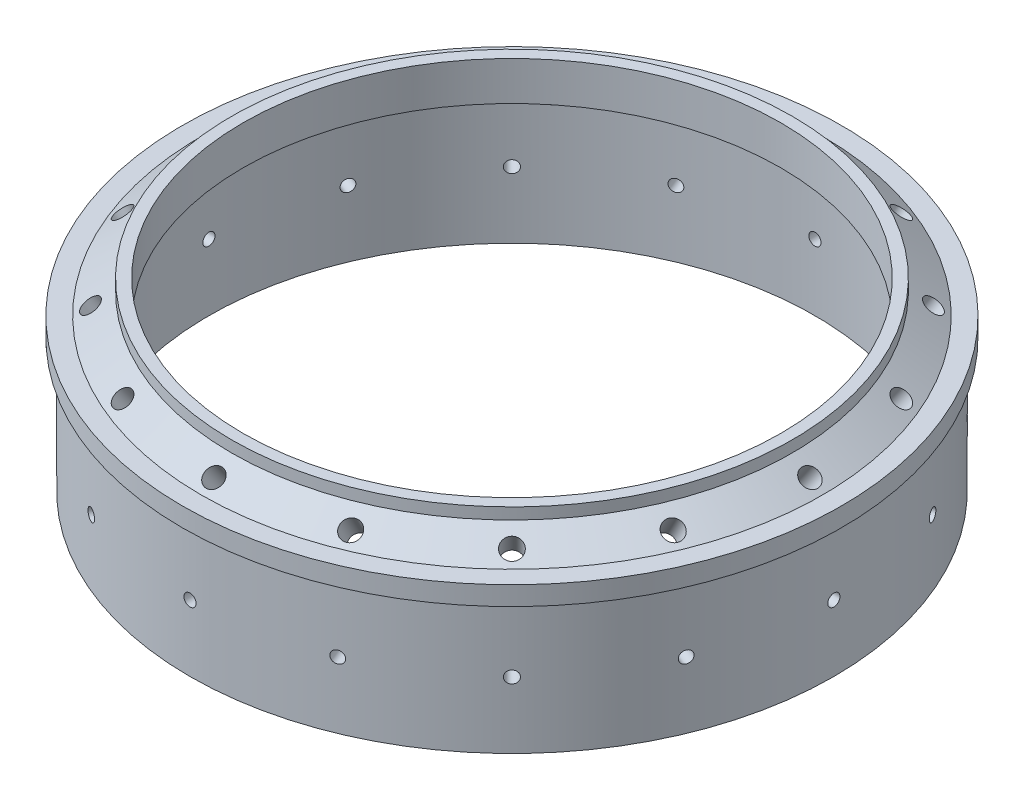
SolidWorks part; units mm, degrees
ref_plane "Front Plane" through (0, 0, 0) normal (0, 0, 1) x (1, 0, 0)
ref_plane "Top Plane" through (0, 0, 0) normal (0, 1, 0) x (1, 0, 0)
ref_plane "Right Plane" through (0, 0, 0) normal (1, 0, 0) x (0, 0, -1)
sketch "Sketch1" plane through (0, 0, 0) normal (0, 0, 1) x (1, 0, 0)
  line L0 (0, 0) -> (-87, 0) construction
  line L1 (-87, 0) -> (-87, -4)
  line L4 (-87, -4) -> (-85, -4)
  line L5 (-85, -4) -> (-85, -39)
  line L6 (-85, -39) -> (-80, -39)
  line L9 (0, 0) -> (0, -25.8501) construction
  line L16 (-80, -7) -> (-71, -0.6981)
  line L17 (-87, 0) -> (-87, 1)
  line L18 (-87, 1) -> (-82, 1)
  line L19 (-82, 1) -> (-74, 6.6017)
  line L20 (-74, 6.6017) -> (-74, 9.6017)
  line L21 (-74, 9.6017) -> (-71, 9.6017)
  line L24 (-80, -7) -> (-80, -39)
  line L31 (-71, -7) -> (-80, -7) construction
  line L33 (-71, 9.6017) -> (-71, -0.6981)
  line L34 (-71, -0.6981) -> (-71, -7) construction
  dimension "D1" = 87
  dimension "D2" = 35
  dimension "D3" = 9
  dimension "D4" = 5
  dimension "D5" = 2
  dimension "D6" = 35
  dimension "D7" = 32
  dimension "D8" = 3
  dimension "D9" = 5
  dimension "D10" = 1
  dimension "D11" = 3
  dimension "D12" = 5
revolve "Revolve1" add sketch "Sketch1" angle 360 about L9
sketch "Sketch2" plane through (0, 0, 0) normal (0, 0, 1) x (1, 0, 0)
  line L0 (-74, 6.6017) -> (-82, 1) construction
  line L1 (-74, 6.6017) -> (-74, 1) construction
  line L2 (-74, 1) -> (-82, 1) construction
  point P4 (-78.671, 3.331)
  dimension "D1" = 4.671
hole_wizard "Ø4.2mm Dowel Hole1" positions "3DSketch1" profile "Sketch3" hole size "Ø5.0" standard "DIN" end condition up to next
sketch3d "3DSketch1"
  point P0 (-78.671, 3.331, 0)
sketch "Sketch3" plane through (-78.671, 3.331, 0) normal (0, 0, 1) x (-0.8192, -0.5736, 0)
  line L0 (0, 0) -> (0, 7.7004)
  line L1 (0, 7.7004) -> (2.5, 7.7004)
  line L2 (2.5, 7.7004) -> (2.5, 0)
  line L5 (2.5, 0) -> (0, 0)
  line L11 (0, -6.35) -> (0, 107.95) construction
  dimension "Thru Hole Dia." = 5
  dimension "Thru Hole Depth" = 7.7004
pattern_circular "CirPattern1" count 16 over 360 about axis through (0, 6.6017, 0) along (0, 1, 0) of "Ø4.2mm Dowel Hole1"
ref_plane "Plane1" through (0, 0, -85) normal (0, 0, -1) x (-1, 0, 0)
sketch "Sketch4" plane through (0, 0, -85) normal (0, 0, -1) x (-1, 0, 0)
  line L0 (-85, -39) -> (85, -39) construction
  circle A0 centre (0, -21.5) radius 1.6
  point P0 (0, -21.5)
  dimension "D2" = 3.2
  dimension "D1" = 17.5
extrude "Cut-Extrude1" cut sketch "Sketch4" against normal up to next
pattern_circular "CirPattern3" count 16 over 360 about axis through (0, 0, 0) along (0, 1, 0) of "Cut-Extrude1" reverse direction yes
equation "\"D1@Sketch2\"=4+cos(35)*cos(35)"
